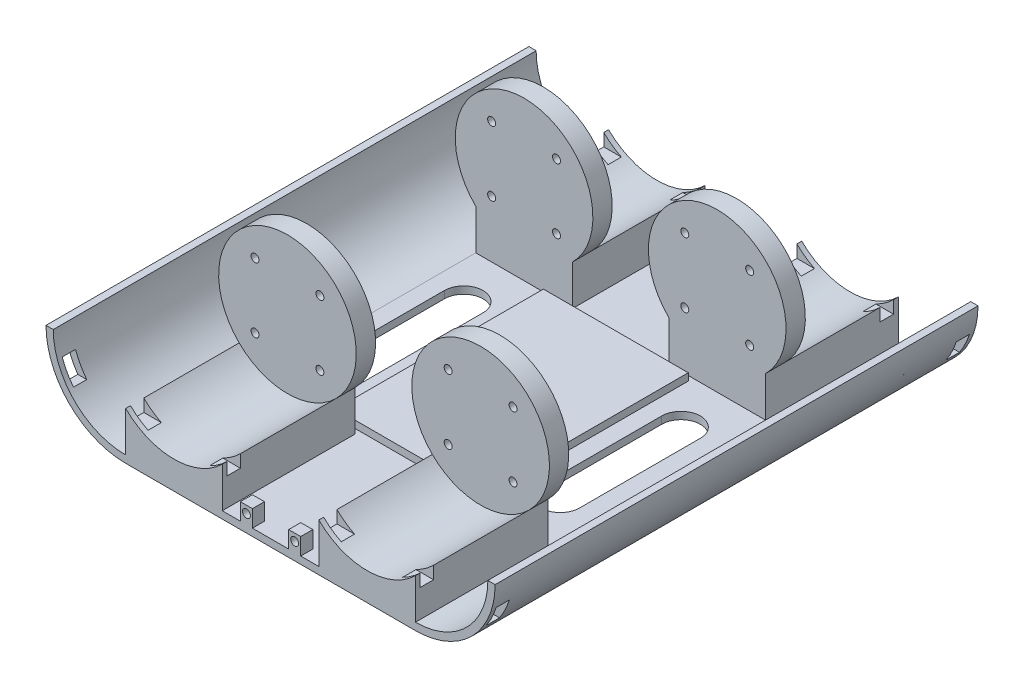
SolidWorks part; units mm, degrees
ref_plane "前视基准面" through (0, 0, 0) normal (0, 0, 1) x (1, 0, 0)
ref_plane "上视基准面" through (0, 0, 0) normal (0, 1, 0) x (1, 0, 0)
ref_plane "右视基准面" through (0, 0, 0) normal (1, 0, 0) x (0, 0, -1)
sketch "草图1" plane through (0, 0, 0) normal (0, 1, 0) x (1, 0, 0)
  line L1 (-40, -100) -> (40, -100)
  line L2 (-40, -100) -> (-40, 100)
  line L3 (-40, 100) -> (40, 100)
  line L4 (40, -100) -> (40, 100)
  line L5 (-40, -100) -> (40, 100) construction
  line L6 (-40, 100) -> (40, -100) construction
  line L11 (-90, -100) -> (90, 100) construction
  line L12 (-90, 100) -> (90, -100) construction
  line L13 (60, -100) -> (-60, -100)
  line L14 (60, -100) -> (60, 100)
  line L15 (60, 100) -> (-60, 100)
  line L16 (-60, -100) -> (-60, 100)
  line L17 (60, -100) -> (-60, 100) construction
  line L18 (60, 100) -> (-60, -100) construction
  line L19 (-90, -100) -> (90, -100)
  line L20 (-90, -100) -> (-90, 100)
  line L21 (-90, 100) -> (90, 100)
  line L22 (90, -100) -> (90, 100)
  line L23 (-90, -100) -> (90, 100) construction
  line L24 (-90, 100) -> (90, -100) construction
  point P0 (0, 0)
  point P6 (0, 0)
  point P11 (0, 0)
  point P17 (0, 0)
  dimension "D1" = 80
  dimension "D2" = 200
  dimension "D3" = 180
  dimension "D4" = 200
  dimension "D5" = 120
extrude "凸台-拉伸1" add sketch "草图1" along normal blind 3 contours L16 L13 L2 L15 | L1 L4 L3 L2 | L14 L15 L4 L13 region at (0, 0, 0) region at (-50, 0, 0) region at (50, 0, 0)
sketch "草图3" plane through (60, 0, 0) normal (1, 0, 0) x (0, 0, -1)
  line L0 (66, 0) -> (-66, 0) construction
  line L1 (-100, 3) -> (100, 3)
  line L2 (-100, 3) -> (-100, 0)
  line L3 (-100, 0) -> (100, 0)
  line L4 (100, 3) -> (100, 0)
  line L5 (100, 3) -> (100, 0) construction
  line L6 (-100, 33) -> (100, 33)
  dimension "D1" = 30
revolve "旋转1" add sketch "草图3" angle 90 about L6 region at (60, 1.5, 0) reverse direction yes
sketch "草图5" plane through (-60, 0, 0) normal (-1, 0, 0) x (0, 0, 1)
  line L0 (-100, 33) -> (100, 33)
  line L1 (-100, 3) -> (100, 3)
  line L2 (-100, 3) -> (-100, 0)
  line L3 (-100, 0) -> (100, 0)
  line L4 (100, 3) -> (100, 0)
revolve "旋转2" add sketch "草图5" angle 90 about L0 reverse direction yes
sketch "草图6" plane through (0, 3, 0) normal (0, 1, 0) x (1, 0, 0)
  line L0 (0, -100) -> (0, -53)
  line L1 (60, -100) -> (-60, -100) construction
  line L2 (0, 100) -> (0, 53)
  line L3 (60, 100) -> (-60, 100) construction
  line L4 (0, -53) -> (-40, -53)
  line L5 (0, -53) -> (40, -53)
  line L6 (0, 53) -> (-40, 53)
  line L7 (0, 53) -> (40, 53)
  dimension "D1" = 47
  dimension "D2" = 47
  dimension "D3" = 40
  dimension "D4" = 40
  dimension "D5" = 40
  dimension "D6" = 40
sketch "草图7" plane through (0, 0, 100) normal (0, 0, 1) x (1, 0, 0)
  line L0 (0, 3) -> (0, 40)
  line L2 (0, 3) -> (40, 3) construction
  line L3 (0, 3) -> (-40, 3) construction
  line L4 (60, 19.6961) -> (60, 3)
  line L5 (60, 3) -> (-60, 3) construction
  line L6 (-11.5, 40) -> (-11.5, 3)
  line L7 (11.5, 40) -> (11.5, 3)
  line L8 (20, 19.6961) -> (20, 3)
  line L9 (-60, 19.6961) -> (-60, 3)
  line L10 (-20, 19.6961) -> (-20, 3)
  circle A0 centre (40, 40) radius 28.5
  circle A1 centre (-40, 40) radius 28.5
  arc A4 (-90, 33) -> (-60, 3) centre (-60, 33) ccw construction
  line M7 (60, 3) -> (-60, 3)
  dimension "D4" = 57
  dimension "D5" = 57
  dimension "D1" = 37
  dimension "D2" = 40
  dimension "D3" = 40
  dimension "D6" = 60
extrude "凸台-拉伸4" add sketch "草图7" against normal blind 55 contours A1 | A1 L9 L10 M7 | A0 | A0 L8 L4 M7 region at (40, 8.7821, 100) region at (40, 40, 100) region at (-40, 40, 100) region at (-40, 8.7821, 100)
extrude "切除-拉伸1" cut sketch "草图7<6>" against normal blind 47 contours A1 | A0
sketch "草图7<6>" plane through (0, 0, 100) normal (0, 0, 1) x (1, 0, 0) same geometry as "草图7"
sketch "草图9" plane through (0, 0, 45) normal (0, 0, -1) x (-1, 0, 0)
  line L0 (-40, 3) -> (-40, 40) construction
  line L1 (-60, 3) -> (-20, 3) construction
  line L2 (-40, 40) -> (-40, 59) construction
  line L3 (-40, 40) -> (-53.435, 53.435) construction
  circle A0 centre (-40, 40) radius 19 construction
  circle A1 centre (-53.435, 53.435) radius 1.65
  circle A2 centre (-26.565, 53.435) radius 1.65
  circle A3 centre (-26.565, 26.565) radius 1.65
  circle A4 centre (-53.435, 26.565) radius 1.65
  dimension "D2" = 38
  dimension "D4" = 3.3
  dimension "D1" = 37
  dimension "D3" = 45
  dimension "D5" = 4
extrude "切除-拉伸2" cut sketch "草图9" against normal blind 47 contours A3 | A2 | A4 | A1
sketch "草图10" plane through (0, 0, 45) normal (0, 0, -1) x (-1, 0, 0)
  line L0 (40, 3) -> (40, 40) construction
  line L1 (0, 3) -> (40, 3) construction
  line L2 (-60, 3) -> (60, 3) construction
  line L3 (40, 40) -> (40, 59) construction
  line L4 (40, 59) -> (40, 40)
  line L5 (26.565, 53.435) -> (40, 40) construction
  circle A0 centre (40, 40) radius 19 construction
  circle A1 centre (26.565, 53.435) radius 1.65
  circle A2 centre (53.435, 53.435) radius 1.65
  circle A3 centre (53.435, 26.565) radius 1.65
  circle A4 centre (26.565, 26.565) radius 1.65
  dimension "D2" = 38
  dimension "D4" = 3.3
  dimension "D1" = 37
  dimension "D3" = 45
  dimension "D5" = 4
extrude "切除-拉伸3" cut sketch "草图10" against normal blind 47 contours A1 | A4 | A3 | A2
sketch "草图11" plane through (0, 0, -100) normal (0, 0, -1) x (-1, 0, 0)
  line L0 (0, 3) -> (-40, 3)
  line L1 (0, 3) -> (-40, 3) construction
  line L2 (0, 3) -> (-20, 3)
  line L3 (0, 3) -> (-60, 3)
  line L4 (-40, 3) -> (-40, 40)
  line L5 (-60, 3) -> (-60, 19.6961)
  line L6 (-20, 3) -> (-20, 19.6961)
  line L7 (20, 3) -> (20, 19.6961)
  line L8 (0, 3) -> (40, 3) construction
  line L9 (20, 19.6961) -> (20, 3) construction
  line L10 (60, 3) -> (60, 19.6961)
  line L11 (40, 3) -> (40, 40)
  line L12 (20, 3) -> (60, 3) construction
  circle A0 centre (-40, 40) radius 28.5
  circle A1 centre (40, 40) radius 28.5
  line M8 (60, 3) -> (-60, 3)
  dimension "D1" = 40
  dimension "D2" = 20
  dimension "D3" = 37
extrude "凸台-拉伸5" add sketch "草图11" against normal blind 55 contours A0 | A0 L4 L0 L6 | A0 L5 L4 M8 | A1 L7 L11 M8 | A1 L11 L10 M8 | A1 region at (28.8094, 8.7821, -100) region at (-28.8094, 8.7821, -100) region at (51.1906, 8.7821, -100) region at (29.4986, 14.3744, -100) region at (-29.3056, 65.5457, -100) region at (-51.1906, 8.7821, -100)
extrude "切除-拉伸4" cut sketch "草图11<3>" against normal blind 47 contours A0 | A1
sketch "草图11<3>" plane through (0, 0, -100) normal (0, 0, -1) x (-1, 0, 0) same geometry as "草图11"
sketch "草图14" plane through (0, 0, -53) normal (0, 0, -1) x (-1, 0, 0)
  line L0 (-40, 3) -> (-40, 40) construction
  line L1 (0, 3) -> (-40, 3) construction
  line L2 (40, 3) -> (40, 40) construction
  line L3 (0, 3) -> (40, 3) construction
  line L4 (-40, 40) -> (40, 40) construction
  line L5 (-40, 40) -> (-26.565, 53.435)
  line L6 (40, 40) -> (26.565, 53.435)
  line L7 (-40, 40) -> (-26.565, 26.565)
  line L8 (-40, 40) -> (-53.435, 26.565)
  line L9 (-40, 40) -> (-53.435, 53.435)
  circle A0 centre (-40, 40) radius 19 construction
  circle A1 centre (40, 40) radius 19 construction
  circle A2 centre (-26.565, 53.435) radius 1.65
  circle A3 centre (26.565, 53.435) radius 1.65
  circle A4 centre (-26.565, 26.565) radius 1.65
  circle A5 centre (-53.435, 26.565) radius 1.65
  circle A6 centre (-53.435, 53.435) radius 1.65
  circle A7 centre (53.435, 53.435) radius 1.65
  circle A8 centre (53.435, 26.565) radius 1.65
  circle A9 centre (26.565, 26.565) radius 1.65
  dimension "D1" = 38
  dimension "D2" = 38
  dimension "D5" = 3.3
  dimension "D6" = 3.3
  dimension "D3" = 45
  dimension "D4" = 45
  dimension "D7" = 4
  dimension "D8" = 4
extrude "切除-拉伸5" cut sketch "草图14" against normal blind 47 contours A3 | A2 | A7 | A8 | A9 | A4 | A5 | A6
sketch "草图15" plane through (0, 3, 0) normal (0, 1, 0) x (1, 0, 0)
  line L1 (-30, -43) -> (30, -43)
  line L2 (-30, -43) -> (-30, 43)
  line L3 (-30, 43) -> (30, 43)
  line L4 (30, -43) -> (30, 43)
  line L5 (-30, -43) -> (30, 43) construction
  line L6 (-30, 43) -> (30, -43) construction
  point P0 (0, 0)
  dimension "D1" = 60
  dimension "D2" = 86
extrude "凸台-拉伸6" add sketch "草图15" along normal blind 3 contours L2 L3 L4 L1
sketch "草图17" plane through (0, 0, 100) normal (0, 0, 1) x (1, 0, 0)
  line L0 (0, 0) -> (-10, 0)
  line L1 (60, 0) -> (-60, 0) construction
  line L2 (0, 0) -> (10, 0)
  line L3 (-10, 0) -> (-10, 5)
  line L4 (10, 0) -> (10, 5)
  line L6 (-12.5, 0) -> (-7.5, 0)
  line L7 (-12.5, 0) -> (-12.5, 10)
  line L8 (-12.5, 10) -> (-7.5, 10)
  line L9 (-7.5, 0) -> (-7.5, 10)
  line L10 (-12.5, 0) -> (-7.5, 10) construction
  line L11 (-12.5, 10) -> (-7.5, 0) construction
  line L12 (7.5, 0) -> (12.5, 0)
  line L13 (7.5, 0) -> (7.5, 10)
  line L14 (7.5, 10) -> (12.5, 10)
  line L15 (12.5, 0) -> (12.5, 10)
  line L16 (7.5, 0) -> (12.5, 10) construction
  line L17 (7.5, 10) -> (12.5, 0) construction
  circle A0 centre (-10, 7) radius 1.65
  circle A1 centre (10, 7) radius 1.65
  line M13 (-60, 0) -> (60, 0)
  line M20 (20, 3) -> (-20, 3)
  dimension "D5" = 3.3
  dimension "D8" = 3.3
  dimension "D1" = 10
  dimension "D2" = 10
  dimension "D3" = 5
  dimension "D4" = 7
  dimension "D6" = 5
  dimension "D7" = 7
  dimension "D9" = 10
  dimension "D10" = 5
  dimension "D11" = 5
  dimension "D12" = 10
extrude "凸台-拉伸7" add sketch "草图17" against normal blind 5 contours L9 L3 M13 M20 | L7 L3 M13 M20 | L9 L8 L7 A0 M20 | L15 L14 L13 A1 M20 | L15 L4 M13 M20 | L13 L2 L4 M20 region at (-8.75, 1.5, 100) region at (8.75, 1.5, 100) region at (-11.25, 1.5, 100) region at (-8.75, 3.086, 100) region at (11.25, 1.5, 100) region at (7.586, 6.5, 100)
sketch "草图18" plane through (0, 0, -100) normal (0, 0, -1) x (-1, 0, 0)
  line L0 (0, 0) -> (-10, 0)
  line L1 (-60, 0) -> (60, 0) construction
  line L2 (0, 0) -> (10, 0)
  line L3 (-10, 0) -> (-10, 5)
  line L4 (10, 0) -> (10, 5)
  line L5 (-10, 0) -> (-10, 7)
  line L6 (-12.5, 0) -> (-7.5, 0)
  line L7 (-12.5, 0) -> (-12.5, 10)
  line L8 (-12.5, 10) -> (-7.5, 10)
  line L9 (-7.5, 0) -> (-7.5, 10)
  line L10 (-12.5, 0) -> (-7.5, 10) construction
  line L11 (-12.5, 10) -> (-7.5, 0) construction
  line L12 (7.5, 0) -> (12.5, 0)
  line L13 (7.5, 0) -> (7.5, 10)
  line L14 (7.5, 10) -> (12.5, 10)
  line L15 (12.5, 0) -> (12.5, 10)
  line L16 (7.5, 0) -> (12.5, 10) construction
  line L17 (7.5, 10) -> (12.5, 0) construction
  line L18 (10, 0) -> (10, 7)
  circle A0 centre (-10, 7) radius 1.65
  circle A1 centre (10, 7) radius 1.65
  line M16 (-60, 0) -> (60, 0)
  line M23 (20, 3) -> (-20, 3)
  dimension "D1" = 10
  dimension "D2" = 10
  dimension "D3" = 5
  dimension "D4" = 5
  dimension "D5" = 5
  dimension "D6" = 10
  dimension "D7" = 5
  dimension "D8" = 10
  dimension "D9" = 7
  dimension "D10" = 7
extrude "凸台-拉伸8" add sketch "草图18" against normal blind 5 contours L9 L3 M16 M23 | L7 L3 M16 M23 | A0 L9 L8 L7 M23 | L13 L2 L4 M23 | L15 L4 M16 M23 | A1 L15 L14 L13 M23 region at (8.75, 1.5, -100) region at (-8.75, 1.5, -100) region at (11.25, 1.5, -100) region at (8.75, 3.086, -100) region at (-11.25, 1.5, -100) region at (-7.586, 6.5, -100)
sketch "草图19" plane through (0, 3, 0) normal (0, 1, 0) x (1, 0, 0)
  line L0 (0, 0) -> (-45, 0)
  line L1 (0, 0) -> (45, 0)
  line L2 (-45, -25) -> (-45, 25) construction
  line L3 (-53, -25) -> (-53, 25)
  line L4 (-37, -25) -> (-37, 25)
  line L5 (45, -25) -> (45, 25) construction
  line L6 (37, -25) -> (37, 25)
  line L7 (53, -25) -> (53, 25)
  arc A0 (-53, -25) -> (-37, -25) centre (-45, -25) ccw
  arc A1 (-37, 25) -> (-53, 25) centre (-45, 25) ccw
  arc A2 (37, -25) -> (53, -25) centre (45, -25) ccw
  arc A3 (53, 25) -> (37, 25) centre (45, 25) ccw
  point P6 (-45, 0)
  point P12 (45, 0)
  dimension "D5" = 8
  dimension "D6" = 8
  dimension "D1" = 45
  dimension "D2" = 45
  dimension "D3" = 50
  dimension "D4" = 50
extrude "切除-拉伸6" cut sketch "草图19" against normal blind 11 contours L7 A3 L6 A2 | L4 A1 L3 A0
sketch "草图20" plane through (0, 0, 0) normal (1, 0, 0) x (0, 0, -1)
  line L0 (-100, 33) -> (-100, 0) construction
  line L1 (-98, 23) -> (-92.5, 23)
  line L2 (-98, 23) -> (-98, 14.5)
  line L3 (-98, 14.5) -> (-92.5, 14.5)
  line L4 (-92.5, 23) -> (-92.5, 14.5)
  line L5 (92.5, 23) -> (98, 23)
  line L6 (92.5, 23) -> (92.5, 14.5)
  line L7 (92.5, 14.5) -> (98, 14.5)
  line L8 (98, 23) -> (98, 14.5)
  line L9 (-100, 33) -> (100, 33) construction
  line L10 (100, 0) -> (100, 33) construction
  dimension "D1" = 8.5
  dimension "D2" = 5.5
  dimension "D3" = 2
  dimension "D4" = 10
  dimension "D5" = 8.5
  dimension "D6" = 5.5
  dimension "D7" = 2
  dimension "D8" = 10
extrude "切除-拉伸7" cut sketch "草图20" against normal blind 119 and the other way blind 108
